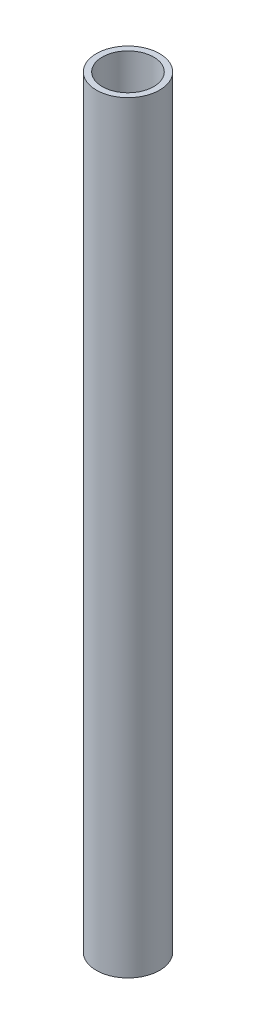
SolidWorks part; units mm, degrees
ref_plane "Front Plane" through (0, 0, 0) normal (0, 0, 1) x (1, 0, 0)
ref_plane "Top Plane" through (0, 0, 0) normal (0, 1, 0) x (1, 0, 0)
ref_plane "Right Plane" through (0, 0, 0) normal (1, 0, 0) x (0, 0, -1)
sketch "Sketch1" plane through (0, 0, 0) normal (0, 1, 0) x (1, 0, 0)
  circle A0 centre (0, 0) radius 21.082
  circle A1 centre (0, 0) radius 17.1133
  dimension "D1" = 42.164
  dimension "D2" = 34.2265
extrude "Boss-Extrude1" add sketch "Sketch1" along normal blind 508
